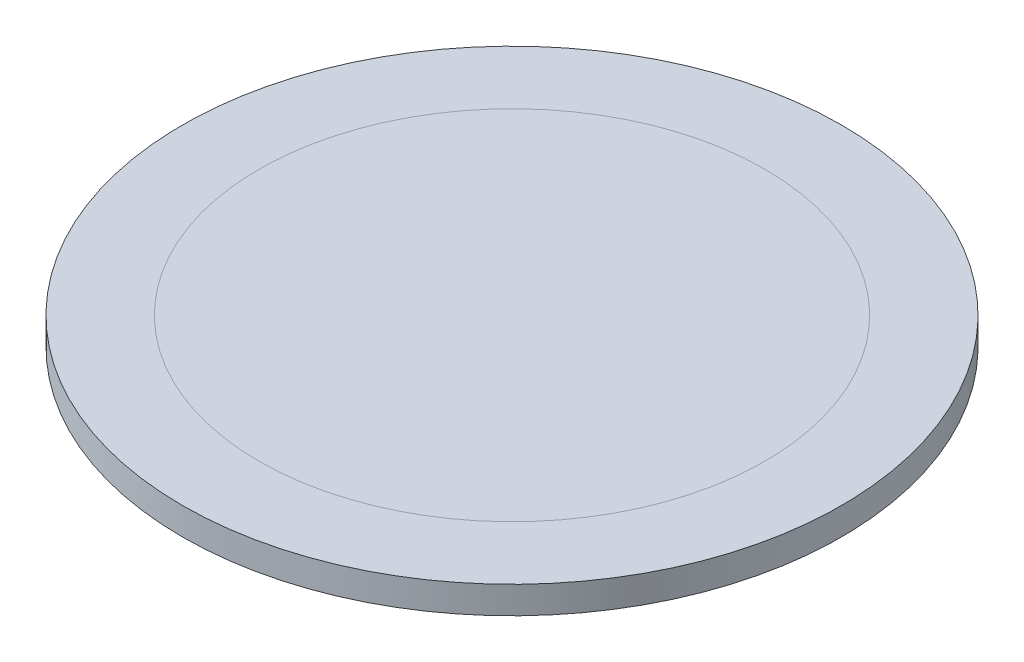
SolidWorks part; units mm, degrees
ref_plane "Ebene vorne" through (0, 0, 0) normal (0, 0, 1) x (1, 0, 0)
ref_plane "Ebene oben" through (0, 0, 0) normal (0, 1, 0) x (1, 0, 0)
ref_plane "Ebene rechts" through (0, 0, 0) normal (1, 0, 0) x (0, 0, -1)
sketch "Skizze1" plane through (0, 0, 0) normal (0, 1, 0) x (1, 0, 0)
  circle A0 centre (0, 0) radius 21.5
  circle A1 centre (0, 0) radius 16.5
extrude "Aufsatz-Linear austragen1" add sketch "Skizze1" along normal offset from surface (1.78 mm away) 5 contours A1 | A0 A1 region at (-20.8919, 0, 0) region at (0, 0, 0)
split line "Trennlinie1"
sketch "Skizze1<3>" plane through (0, 0, 0) normal (0, 1, 0) x (1, 0, 0) same geometry as "Skizze1"
